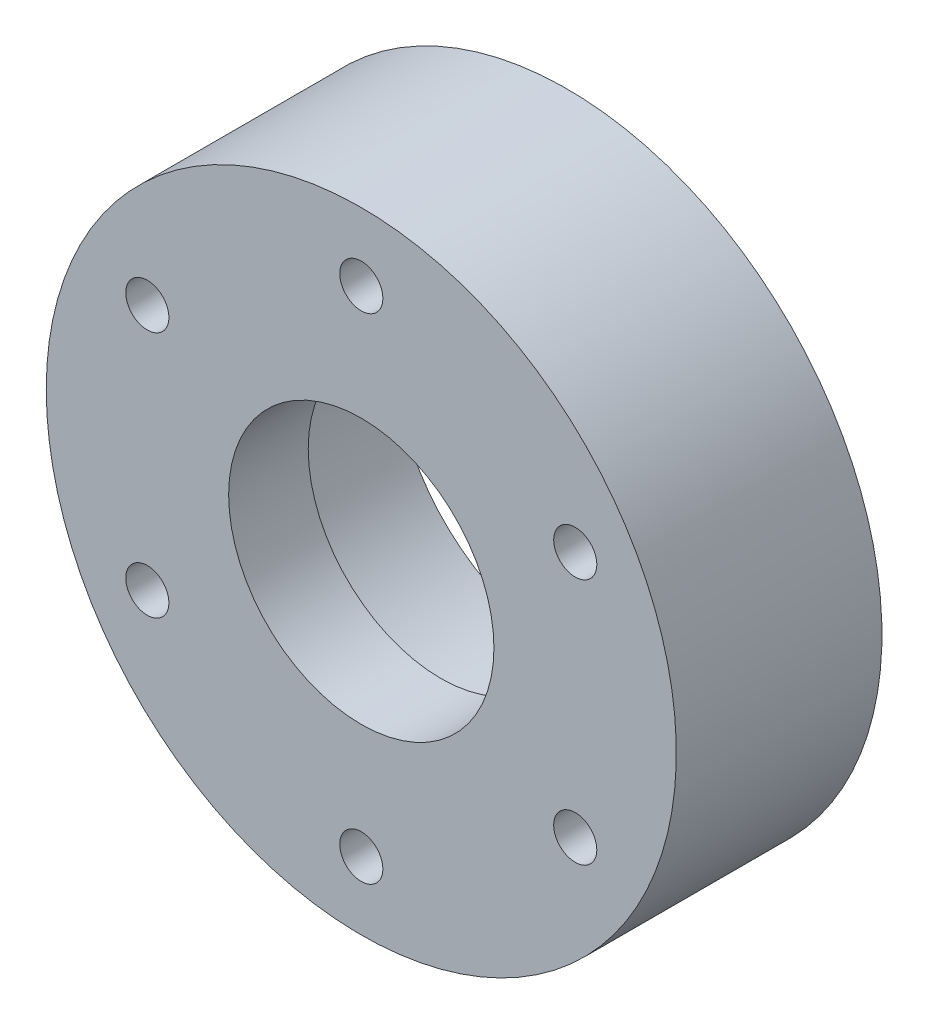
SolidWorks part; units mm, degrees
ref_plane "Front Plane" through (0, 0, 0) normal (0, 0, 1) x (1, 0, 0)
ref_plane "Top Plane" through (0, 0, 0) normal (0, 1, 0) x (1, 0, 0)
ref_plane "Right Plane" through (0, 0, 0) normal (1, 0, 0) x (0, 0, -1)
sketch "Sketch1" plane through (0, 0, -159.9523) normal (1, 0, 0) x (0, 0, -1)
  line L0 (0, 0) -> (-62.4415, 0) construction
  line L1 (-31, 47.5) -> (0, 47.5)
  line L2 (0, 47.5) -> (0, 26)
  line L3 (0, 26) -> (-19, 26)
  line L4 (-19, 26) -> (-19, 20)
  line L5 (-19, 20) -> (-31, 20)
  line L6 (-31, 20) -> (-31, 47.5)
  dimension "D1" = 40
  dimension "D2" = 52
  dimension "D3" = 12
  dimension "D4" = 19
  dimension "D5" = 31
  dimension "D6" = 95
revolve "Revolve1" add sketch "Sketch1" angle 360 about L0
sketch "Sketch2" plane through (0, 0, -128.9523) normal (0, 0, 1) x (1, 0, 0)
  circle A1 centre (0, 37.25) radius 3.25
  circle A2 centre (0, 37.25) radius 3.25
  dimension "D1" = 0
extrude "Cut-Extrude1" cut sketch "Sketch2" against normal through all
pattern_circular "CirPattern1" count 6 over 360 about axis through (0, 0, -159.9523) along (0, 0, -1) of "Cut-Extrude1" reverse direction yes
